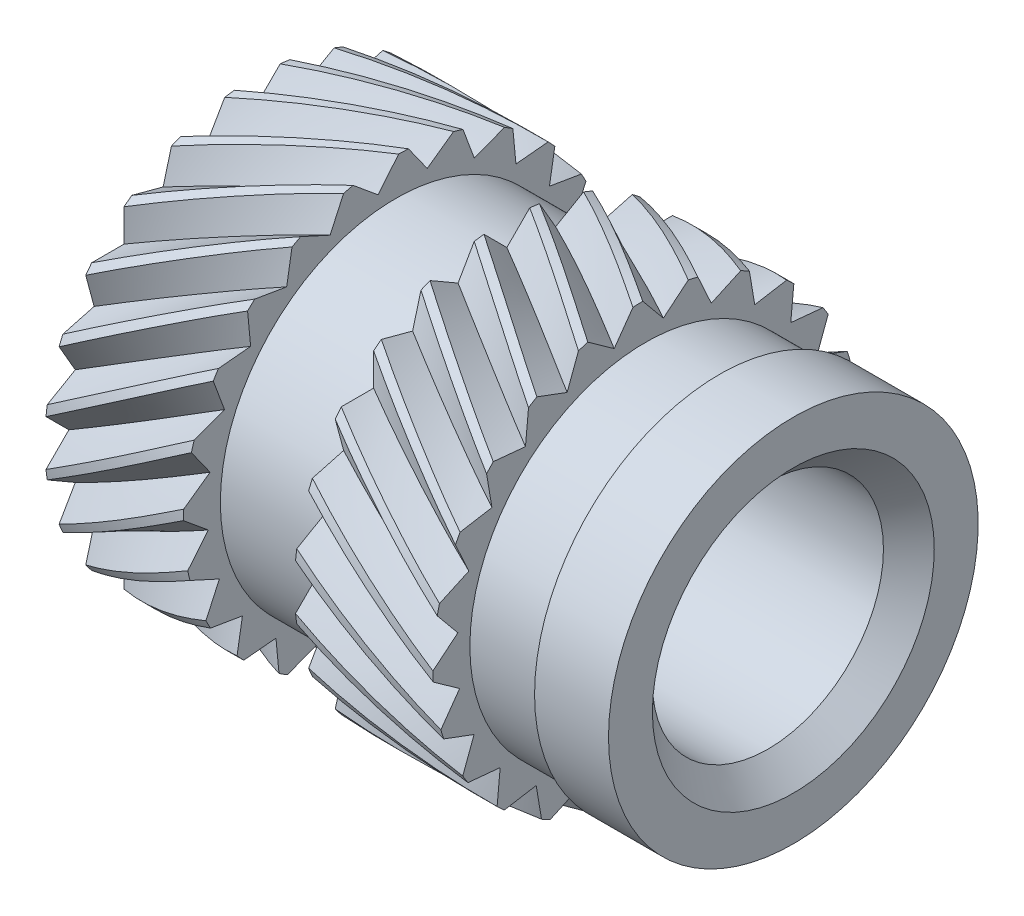
SolidWorks part; units mm, degrees
material "ЛС59-1 ГОСТ 15527-2004"
ref_plane "Front" through (0, 0, 0) normal (0, 0, 1) x (1, 0, 0)
ref_plane "Top" through (0, 0, 0) normal (0, 1, 0) x (1, 0, 0)
ref_plane "Right" through (0, 0, 0) normal (1, 0, 0) x (0, 0, -1)
sketch "Эскиз1" plane through (0, 0, 0) normal (0, 0, 1) x (1, 0, 0)
  line L0 (0, 1) -> (0, 2.3)
  line L1 (0, 2.3) -> (1.5, 2.3)
  line L2 (1.5, 2.3) -> (1.5, 1.9)
  line L3 (1.5, 1.9) -> (2.7, 1.9)
  line L4 (2.7, 1.9) -> (2.7, 2.3)
  line L5 (2.7, 2.3) -> (4.2, 2.3)
  line L6 (4.2, 2.3) -> (4.2, 1.9)
  line L7 (4.2, 1.9) -> (5, 1.9)
  line L8 (5, 1.9) -> (5, 2)
  line L9 (5, 2) -> (5.8, 2)
  line L10 (5.8, 2) -> (5.8, 1)
  line L11 (5.8, 1) -> (0, 1)
  line L12 (0, 0) -> (5.7184, 0) construction
  dimension "D1" = 4.6
  dimension "D2" = 2
  dimension "D3" = 3.8
  dimension "D4" = 3.8
  dimension "D5" = 4
  dimension "D6" = 5.8
  dimension "D7" = 0.8
  dimension "D8" = 0.8
  dimension "D9" = 1.5
revolve "Повернуть1" add sketch "Эскиз1" angle 360 about L12
hole_wizard "Отверстие обработанное метчиком M31" positions "Эскиз3" profile "Эскиз2" tap size "M3" standard "Din" end condition through all
sketch "Эскиз3" plane through (0, 0, 0) normal (-1, 0, 0) x (0, 0, 1)
  point P0 (0, 0)
sketch "Эскиз2" plane through (0, 0, 0) normal (0, 1, 0) x (0, 0, 1)
  line L0 (0, 0) -> (0, 5.8)
  line L1 (0, 5.8) -> (1.525, 5.8)
  line L2 (1.25, 5.525) -> (1.25, 0.275)
  line L3 (1.25, 0.275) -> (1.525, 0)
  line L5 (1.525, 0) -> (0, 0)
  line L6 (-1.25, 0.275) -> (-1.525, 0) construction
  line L7 (1.525, 5.8) -> (1.25, 5.525)
  line L8 (-1.525, 5.8) -> (-1.25, 5.525) construction
  line L11 (0, -6.35) -> (0, 107.95) construction
  dimension "Диаметр проходного сверла" = 2.5
  dimension "Глубина проходного сверла" = 5.8
  dimension "Диаметр передней зенковки" = 3.05
  dimension "Угол передней зенковки" = 90
  dimension "Диаметр задней зенковки" = 3.05
  dimension "Угол задней зенковки" = 90
cosmetic thread "Отверстие резьбы1" parameters "D2"=3
sketch "Эскиз4" plane through (0, 0, 0) normal (-1, 0, 0) x (0, 0, 1)
  circle A1 centre (0, 0) radius 2.3
  circle A2 centre (0, 0) radius 2.3
  dimension "D1" = 0
curve "Спираль1" pitch 22 height 1.76 turns 0.08
sketch "Эскиз5" plane through (0, 0, 0) normal (-1, 0, 0) x (0, 0, 1)
  line L0 (2.2866, 0.2475) -> (2.0392, 0)
  line L1 (2.0392, 0) -> (2.2866, -0.2475)
  line L2 (0, 0) -> (2.0392, 0) construction
  circle A0 centre (0, 0) radius 2.3 construction
  arc A1 (2.2866, -0.2475) -> (2.2866, 0.2475) centre (0, 0) ccw
  dimension "D1" = 0.35
sweep "Вырез-По траектории1" cut profiles "Эскиз5" path "Спираль1" align with end faces yes
sketch "Эскиз6" plane through (2.7, 0, 0) normal (-1, 0, 0) x (0, 0, 1)
  circle A1 centre (0, 0) radius 2.3
  circle A2 centre (0, 0) radius 2.3
  dimension "D1" = 0
curve "Спираль2" pitch 22 height 1.76 turns 0.08
sketch "Эскиз7" plane through (2.7, 0, 0) normal (-1, 0, 0) x (0, 0, 1)
  line L2 (2.2866, 0.2475) -> (2.0392, 0)
  line L3 (2.0392, 0) -> (2.2866, -0.2475)
  line L4 (2.2866, 0.2475) -> (2.0392, 0)
  line L5 (2.0392, 0) -> (2.2866, -0.2475)
  arc A1 (2.2866, -0.2475) -> (2.2866, 0.2475) centre (0, 0) ccw
  arc A2 (2.2866, -0.2475) -> (2.2866, 0.2475) centre (0, 0) ccw
  dimension "D1" = 0
sweep "Вырез-По траектории2" cut profiles "Эскиз7" path "Спираль2" align with end faces yes
pattern_circular "Круговой массив1" count 24 over 360 about axis through (0, 0, 0) along (-1, 0, 0) of "Вырез-По траектории1", "Вырез-По траектории2"
